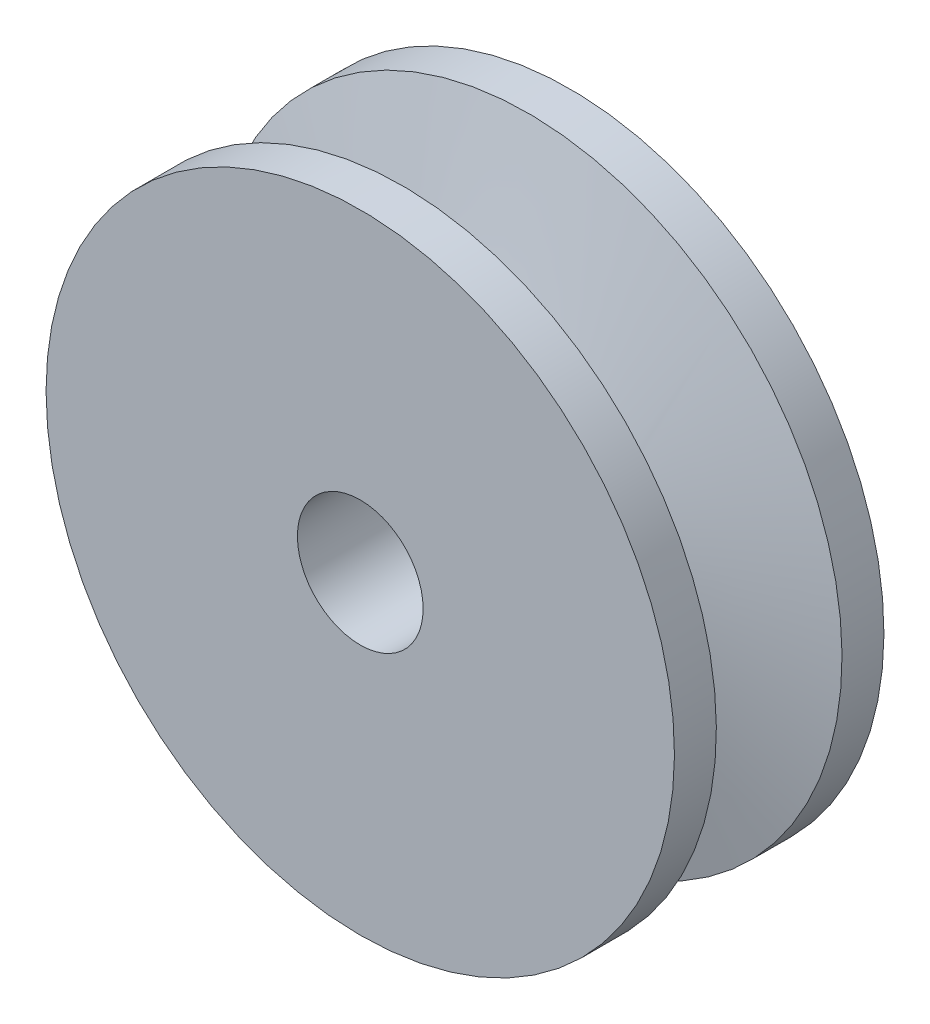
SolidWorks part; units mm, degrees
ref_plane "Front Plane" through (0, 0, 0) normal (0, 0, 1) x (1, 0, 0)
ref_plane "Top Plane" through (0, 0, 0) normal (0, 1, 0) x (1, 0, 0)
ref_plane "Right Plane" through (0, 0, 0) normal (1, 0, 0) x (0, 0, -1)
sketch "Sketch1" plane through (0, 0, 0) normal (0, 0, 1) x (1, 0, 0)
  circle A0 centre (0, 0) radius 35
  dimension "D1" = 70
extrude "Boss-Extrude1" add sketch "Sketch1" along normal mid plane 10
ref_plane "Plane1" through (0, 0, -15) normal (0, 0, -1) x (-1, 0, 0)
sketch "Sketch2" plane through (0, 0, -15) normal (0, 0, -1) x (-1, 0, 0)
  circle A0 centre (0, 0) radius 75
  dimension "D1" = 150
extrude "Boss-Extrude2" add sketch "Sketch2" along normal blind 10 separate body
loft "Loft2" add section edge at (35, 0, -5) section edge at (-75, 0, -15) connector at (30.6389, 16.9192, -5) connector at (47.9156, 57.6983, -15)
mirror "Mirror4" about plane through (0, 0, 0) normal (0, 0, 1) of "Boss-Extrude2", "Loft2"
sketch "Sketch3" plane through (0, 0, -25) normal (0, 0, -1) x (-1, 0, 0)
  circle A0 centre (0, 0) radius 15
  dimension "D1" = 30
extrude "Cut-Extrude1" cut sketch "Sketch3" against normal up to next
